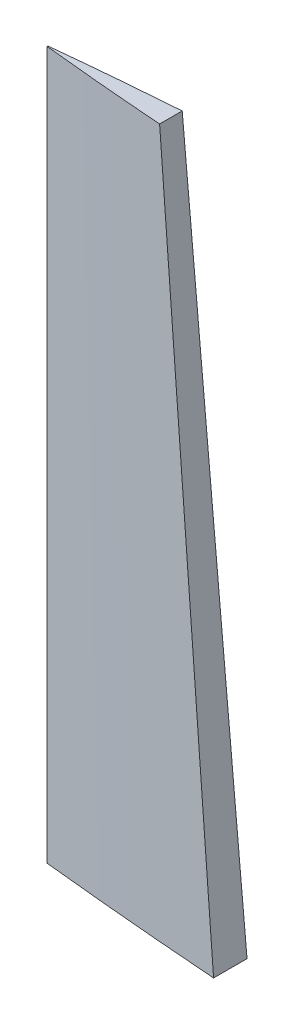
SolidWorks part; units mm, degrees
ref_plane "Front Plane" through (0, 0, 0) normal (0, 0, 1) x (1, 0, 0)
ref_plane "Top Plane" through (0, 0, 0) normal (0, 1, 0) x (1, 0, 0)
ref_plane "Right Plane" through (0, 0, 0) normal (1, 0, 0) x (0, 0, -1)
ref_plane "Plane1" through (0, 22, 0) normal (0, 1, 0) x (1, 0, 0)
sketch "Sketch1" plane through (0, 22, 0) normal (0, 1, 0) x (1, 0, 0)
  line L0 (-118.3161, 4.4015) -> (-118.3161, -4.4015)
  line L1 (-166.383, 0.1514) -> (-166.383, -0.1514)
  spline S0 degree 3 poles (-118.3161, 4.4015) (-118.496, 4.3888) (-121.1673, 4.2003) (-126.1821, 3.812) (-133.1891, 3.2525) (-139.6818, 2.7033) (-145.5894, 2.1811) (-150.8471, 1.6969) (-155.3973, 1.2627) (-159.1901, 0.8894) (-162.1841, 0.5871) (-164.3463, 0.3645) (-165.6532, 0.2281) (-166.2367, 0.1668) (-166.383, 0.1514) knots 0 0 0 0 0.011212 0.166483 0.312686 0.448211 0.571563 0.681381 0.776452 0.855723 0.918312 0.963525 0.990856 1 1 1 1
  spline S1 degree 3 poles (-118.3161, -4.4015) (-118.496, -4.3888) (-121.1673, -4.2003) (-126.1821, -3.812) (-133.1891, -3.2525) (-139.6818, -2.7033) (-145.5894, -2.1811) (-150.8471, -1.6969) (-155.3973, -1.2627) (-159.1901, -0.8894) (-162.1841, -0.5871) (-164.3463, -0.3645) (-165.6532, -0.2281) (-166.2367, -0.1668) (-166.383, -0.1514) knots 0 0 0 0 0.011212 0.166483 0.312686 0.448211 0.571563 0.681381 0.776452 0.855723 0.918312 0.963525 0.990856 1 1 1 1
ref_plane "Plane2" through (0, 207.979, 0) normal (0, 1, 0) x (1, 0, 0)
sketch "Sketch2" plane through (0, 207.979, 0) normal (0, 1, 0) x (1, 0, 0)
  line L0 (-133.9383, 2.971) -> (-133.9383, -2.971)
  line L1 (-166.383, 0.1022) -> (-166.383, -0.1022)
  spline S0 degree 3 poles (-133.9383, 2.971) (-134.0597, 2.9624) (-135.8629, 2.8352) (-139.2478, 2.573) (-143.9774, 2.1954) (-148.36, 1.8247) (-152.3476, 1.4722) (-155.8964, 1.1454) (-158.9678, 0.8523) (-161.5279, 0.6003) (-163.5488, 0.3963) (-165.0083, 0.246) (-165.8904, 0.154) (-166.2843, 0.1126) (-166.383, 0.1022) knots 0 0 0 0 0.011212 0.166483 0.312686 0.448211 0.571563 0.681381 0.776452 0.855723 0.918312 0.963525 0.990856 1 1 1 1
  spline S1 degree 3 poles (-133.9383, -2.971) (-134.0597, -2.9624) (-135.8629, -2.8352) (-139.2478, -2.573) (-143.9774, -2.1954) (-148.36, -1.8247) (-152.3476, -1.4722) (-155.8964, -1.1454) (-158.9678, -0.8523) (-161.5279, -0.6003) (-163.5488, -0.3963) (-165.0083, -0.246) (-165.8904, -0.154) (-166.2843, -0.1126) (-166.383, -0.1022) knots 0 0 0 0 0.011212 0.166483 0.312686 0.448211 0.571563 0.681381 0.776452 0.855723 0.918312 0.963525 0.990856 1 1 1 1
loft "Loft1" add profiles "Sketch1", "Sketch2" connector at (-118.3161, 22, -4.4015) connector at (-133.9383, 207.979, -2.971)
